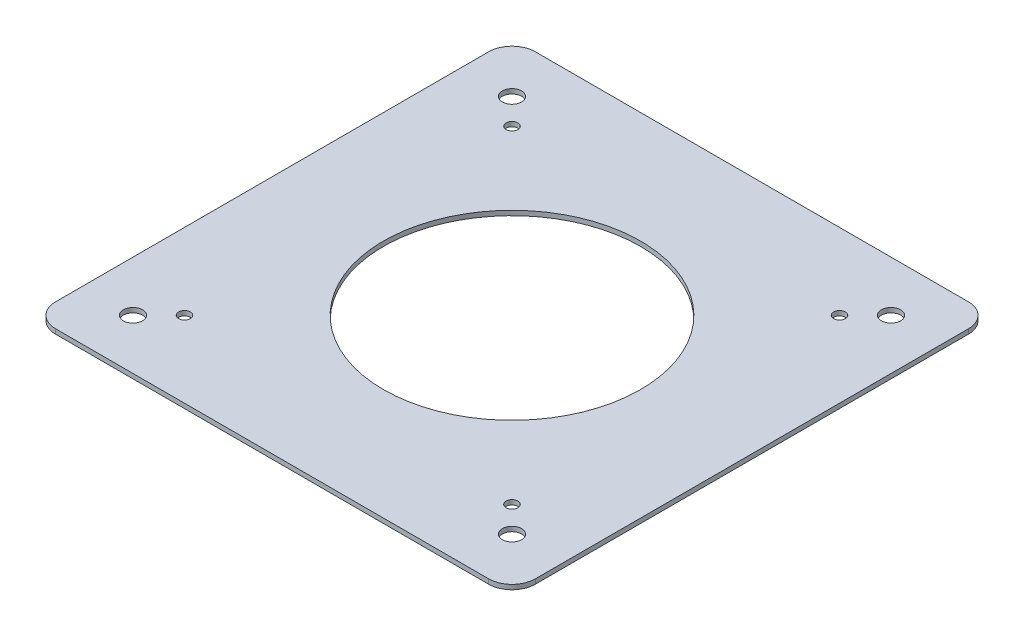
SolidWorks part; units mm, degrees
ref_plane "Front Plane" through (0, 0, 0) normal (0, 0, 1) x (1, 0, 0)
ref_plane "Top Plane" through (0, 0, 0) normal (0, 1, 0) x (1, 0, 0)
ref_plane "Right Plane" through (0, 0, 0) normal (1, 0, 0) x (0, 0, -1)
sketch "Sketch1" plane through (0, 0, 0) normal (0, 1, 0) x (1, 0, 0)
  line L1 (-46.2, -51.2) -> (46.2, -51.2)
  line L2 (-51.2, -46.2) -> (-51.2, 46.2)
  line L3 (-46.2, 51.2) -> (46.2, 51.2)
  line L4 (51.2, -46.2) -> (51.2, 46.2)
  line L5 (-51.2, -51.2) -> (51.2, 51.2) construction
  line L6 (-51.2, 51.2) -> (51.2, -51.2) construction
  arc A0 (-46.2, -51.2) -> (-51.2, -46.2) centre (-46.2, -46.2) cw
  arc A1 (-51.2, 46.2) -> (-46.2, 51.2) centre (-46.2, 46.2) cw
  arc A2 (46.2, -51.2) -> (51.2, -46.2) centre (46.2, -46.2) ccw
  arc A3 (46.2, 51.2) -> (51.2, 46.2) centre (46.2, 46.2) cw
  point P0 (0, 0)
  dimension "D3" = 5
  dimension "D1" = 102.4
  dimension "D2" = 102.4
sketch "Sketch7" plane through (0, 0, 0) normal (0, 0, 1) x (1, 0, 0)
  line L0 (0, 0) -> (0, 67.6191) construction
base flange "Base-Flange1" sketch "Sketch1" thickness 1 reverse thickness direction no parameters "D1"=1
sketch "Sketch6" plane through (0, 0, 0) normal (0, 1, 0) x (1, 0, 0)
  circle A0 centre (0, 0) radius 27.45
  dimension "D1" = 54.9
extrude "Cut-Extrude1" cut sketch "Sketch6" against normal blind 10 normal cut yes
sketch "Sketch8" plane through (0, 0, 0) normal (0, 1, 0) x (1, 0, 0)
  line L0 (51.2, -46.2) -> (51.2, 46.2) construction
  line L1 (46.2, 51.2) -> (-46.2, 51.2) construction
  circle A0 centre (40.45, 40.45) radius 2.05
  circle A1 centre (34.95, 34.95) radius 1.25
  dimension "D3" = 4.1
  dimension "D6" = 2.5
  dimension "D1" = 10.75
  dimension "D2" = 10.75
  dimension "D4" = 16.25
  dimension "D5" = 16.25
extrude "Cut-Extrude2" cut sketch "Sketch8" against normal blind 10 normal cut yes
pattern_circular "CirPattern1" count 4 over 360 about axis through (0, 0, 0) along (0, 1, 0) of "Cut-Extrude2"
sketch "Bend-Lines1" plane through (0, 0, 0) normal (0, 1, 0) x (1, 0, 0)
sketch "Bounding-Box1" plane through (0, 0, 0) normal (0, 1, 0) x (1, 0, 0)
sheet metal parameters "Sheet-Metal(1)" thickness 1 parameters "D1"=1
flat pattern "Flat-Pattern(1)" [suppressed]
sketch "Bend-Lines2" plane through (0, 0, 0) normal (0, 1, 0) x (1, 0, 0)
sketch "Bounding-Box2" [suppressed] plane through (0, 0, 0) normal (0, 1, 0) x (1, 0, 0)
sheet metal parameters "Sheet-Metal(2)" thickness 1 parameters "D1"=1
flat pattern "Flat-Pattern(1)"
sketch "Bend-Lines2" plane through (0, 0, 0) normal (0, 1, 0) x (1, 0, 0)
sketch "Bounding-Box2" [suppressed] plane through (0, 0, 0) normal (0, 1, 0) x (1, 0, 0)
sheet metal parameters "Sheet-Metal(3)" thickness 1 parameters "D1"=1
flat pattern "Flat-Pattern(1)"
sketch "Bend-Lines2" plane through (0, 0, 0) normal (0, 1, 0) x (1, 0, 0)
sketch "Bounding-Box2" [suppressed] plane through (0, 0, 0) normal (0, 1, 0) x (1, 0, 0)
sheet metal parameters "Sheet-Metal(4)" thickness 1 parameters "D1"=1
flat pattern "Flat-Pattern(1)"
sketch "Bend-Lines2" plane through (0, 0, 0) normal (0, 1, 0) x (1, 0, 0)
sketch "Bounding-Box2" [suppressed] plane through (0, 0, 0) normal (0, 1, 0) x (1, 0, 0)
